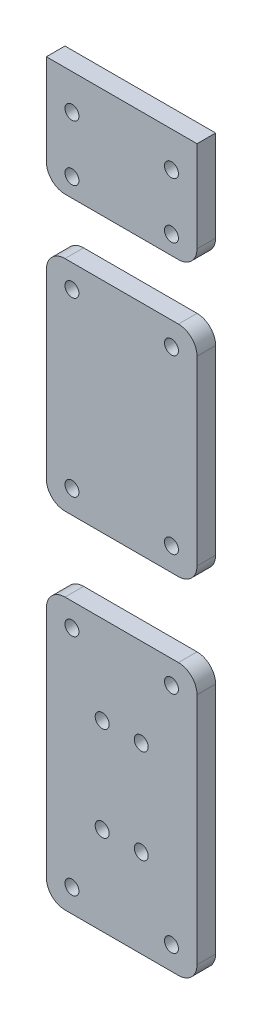
SolidWorks part; units mm, degrees
ref_plane "Front Plane" through (0, 0, 0) normal (0, 0, 1) x (1, 0, 0)
ref_plane "Top Plane" through (0, 0, 0) normal (0, 1, 0) x (1, 0, 0)
ref_plane "Right Plane" through (0, 0, 0) normal (1, 0, 0) x (0, 0, -1)
sketch "Sketch1" plane through (0, 0, 0) normal (0, 0, 1) x (1, 0, 0)
  line L0 (4, 26) -> (2, 26)
  line L1 (0, 1.5) -> (16.2, 1.5) construction
  line L2 (0, 14) -> (4, 14) construction
  line L3 (0, 14) -> (0, 1.5) construction
  line L4 (6, 14) -> (6, 26)
  line L5 (4, 14) -> (4, 26)
  line L6 (0, 28) -> (0, 53.14)
  line L7 (0, 94.665) -> (0, 104.46)
  line L8 (6, 14) -> (10.2, 14) construction
  line L9 (8.1, 1.5) -> (8.1, 104.46) construction
  line L10 (0, 104.46) -> (16.2, 104.46)
  line L11 (6, 63.14) -> (10.2, 63.14)
  line L12 (6, 55.14) -> (10.2, 55.14)
  line L13 (6, 92.665) -> (10.2, 92.665)
  line L14 (6, 86.665) -> (10.2, 86.665)
  line L15 (16.2, 84.665) -> (16.2, 65.14)
  line L16 (10.2, 86.665) -> (10.2, 92.665)
  line L17 (14.2, 55.14) -> (12.2, 55.14)
  line L18 (2, 92.665) -> (4, 92.665)
  line L19 (2, 86.665) -> (4, 86.665)
  line L20 (2, 63.14) -> (4, 63.14)
  line L21 (10.2, 55.14) -> (10.2, 63.14)
  line L22 (4, 86.665) -> (4, 92.665)
  line L23 (4, 55.14) -> (4, 63.14)
  line L24 (6, 55.14) -> (6, 63.14)
  line L25 (2, 55.14) -> (4, 55.14)
  line L26 (6, 86.665) -> (6, 92.665)
  line L27 (12.2, 55.14) -> (12.2, 63.14)
  line L28 (12.2, 86.665) -> (12.2, 92.665)
  line L29 (14.2, 63.14) -> (12.2, 63.14)
  line L30 (14.2, 86.665) -> (12.2, 86.665)
  line L31 (14.2, 92.665) -> (12.2, 92.665)
  line L32 (6, 26) -> (10.2, 26)
  line L33 (4, 14) -> (6, 14)
  line L34 (16.2, 94.665) -> (16.2, 104.46)
  line L35 (16.2, 28) -> (16.2, 53.14)
  line L36 (12.2, 14) -> (12.2, 26)
  line L37 (10.2, 14) -> (10.2, 26)
  line L38 (16.2, 14) -> (16.2, 1.5) construction
  line L39 (16.2, 14) -> (12.2, 14) construction
  line L40 (12.2, 26) -> (14.2, 26)
  line L41 (10.2, 14) -> (12.2, 14)
  line L58 (0, 84.665) -> (0, 65.14)
  circle A0 centre (2.85, 11.5) radius 0.75 construction
  circle A1 centre (13.45, 94.665) radius 0.75
  circle A2 centre (13.45, 84.165) radius 0.75
  circle A3 centre (2.85, 5.5) radius 0.75 construction
  circle A4 centre (13.45, 65.64) radius 0.75
  circle A5 centre (13.45, 52.64) radius 0.75
  circle A6 centre (13.45, 28.5) radius 0.75
  circle A7 centre (10.2, 35.5) radius 0.75
  arc A8 (16.2, 28) -> (14.2, 26) centre (14.2, 28) cw
  circle A9 centre (10.2, 45.64) radius 0.75
  arc A10 (2, 86.665) -> (0, 84.665) centre (2, 84.665) ccw
  arc A11 (14.2, 55.14) -> (16.2, 53.14) centre (14.2, 53.14) cw
  circle A12 centre (13.45, 100.665) radius 0.75
  arc A13 (16.2, 94.665) -> (14.2, 92.665) centre (14.2, 94.665) cw
  arc A14 (16.2, 65.14) -> (14.2, 63.14) centre (14.2, 65.14) cw
  arc A15 (0, 65.14) -> (2, 63.14) centre (2, 65.14) ccw
  arc A16 (0, 94.665) -> (2, 92.665) centre (2, 94.665) ccw
  arc A17 (14.2, 86.665) -> (16.2, 84.665) centre (14.2, 84.665) cw
  circle A18 centre (2.75, 100.665) radius 0.75
  circle A19 centre (13.35, 5.5) radius 0.75 construction
  circle A20 centre (13.35, 11.5) radius 0.75 construction
  arc A22 (2, 55.14) -> (0, 53.14) centre (2, 53.14) ccw
  circle A24 centre (6, 45.64) radius 0.75
  arc A26 (0, 28) -> (2, 26) centre (2, 28) ccw
  circle A30 centre (6, 35.5) radius 0.75
  circle A32 centre (2.75, 28.5) radius 0.75
  circle A34 centre (2.75, 52.64) radius 0.75
  circle A36 centre (2.75, 65.64) radius 0.75
  circle A38 centre (2.75, 84.165) radius 0.75
  circle A40 centre (2.75, 94.665) radius 0.75
  point P9 (8.1, 92.665)
  point P11 (8.1, 86.665)
  point P16 (8.1, 63.14)
  point P17 (8.1, 55.14)
  point P20 (8.1, 63.14)
  point P21 (8.1, 55.14)
  point P58 (8.1, 26)
  point P66 (8.1, 14)
  point P83 (8.1, 26)
  point P96 (8.1, 92.665)
  point P100 (8.1, 14)
  dimension "D11" = 2.75
  dimension "D12" = 6
  dimension "D13" = 2.5
  dimension "D14" = 9.5
  dimension "D15" = 2.75
  dimension "D16" = 6
  dimension "D8" = 2
  dimension "D28" = 2
  dimension "D29" = 1.5
  dimension "D30" = 2
  dimension "D31" = 1.5
  dimension "D32" = 2
  dimension "D33" = 1.5
  dimension "D34" = 1.5
  dimension "D35" = 1.5
  dimension "D36" = 1.5
  dimension "D37" = 1.5
  dimension "D38" = 1.5
  dimension "D42" = 1.5
  dimension "D43" = 1.5
  dimension "D44" = 2
  dimension "D2" = 2.85
  dimension "D3" = 4
  dimension "D4" = 2.85
  dimension "D5" = 6
  dimension "D6" = 2.5
  dimension "D7" = 12
  dimension "D9" = 2.5
  dimension "D10" = 9.5
  dimension "D17" = 29.14
  dimension "D18" = 2.75
  dimension "D19" = 2.5
  dimension "D20" = 8
  dimension "D21" = 2
  dimension "D22" = 2
  dimension "D23" = 2
  dimension "D24" = 2
  dimension "D25" = 2.75
  dimension "D26" = 2.5
  dimension "D27" = 23.525
  dimension "D39" = 2
  dimension "D40" = 2.75
  dimension "D41" = 6
  dimension "D45" = 2.75
  dimension "D46" = 6
  dimension "D47" = 11.795
  dimension "D48" = 8.1
  dimension "D49" = 2
extrude "Boss-Extrude1" add sketch "Sketch1" along normal blind 2
sketch "Sketch2" plane through (0, 0, 2) normal (0, 0, 1) x (1, 0, 0)
  line L0 (4, 92.665) -> (12.2, 92.665)
  line L1 (12.2, 92.665) -> (12.2, 86.665)
  line L2 (12.2, 86.665) -> (4, 86.665)
  line L3 (4, 86.665) -> (4, 92.665)
  line L4 (4, 63.14) -> (12.2, 63.14)
  line L5 (12.2, 63.14) -> (12.2, 55.14)
  line L6 (12.2, 55.14) -> (4, 55.14)
  line L7 (4, 55.14) -> (4, 63.14)
  line L8 (4, 26) -> (12.2, 26)
  line L9 (12.2, 26) -> (12.2, 14)
  line L10 (12.2, 14) -> (4, 14)
  line L11 (4, 14) -> (4, 26)
extrude "Cut-Extrude1" cut sketch "Sketch2" against normal up to surface (2 mm away) up to face at (3.5, 94.665, 0)
equation "\"D48@Sketch1\"= ( \"fingerWidth@parametersSketch@prostheticParameters.SLDPRT\" ) / 2 'Ring Width"
equation "\"D17@Sketch1\"= \"HL@parametersSketch@prostheticParameters.SLDPRT\" * 0.244 - 4 - 12'Ring PIP Length"
equation "\"D27@Sketch1\"= \"HL@parametersSketch@prostheticParameters.SLDPRT\" * 0.165 - 3 - 4'Ring MIP Length"
equation "\"D47@Sketch1\"= \"HL@parametersSketch@prostheticParameters.SLDPRT\" * 0.107 - 3 - 5'Ring DIP Length - Gap fingertip"
